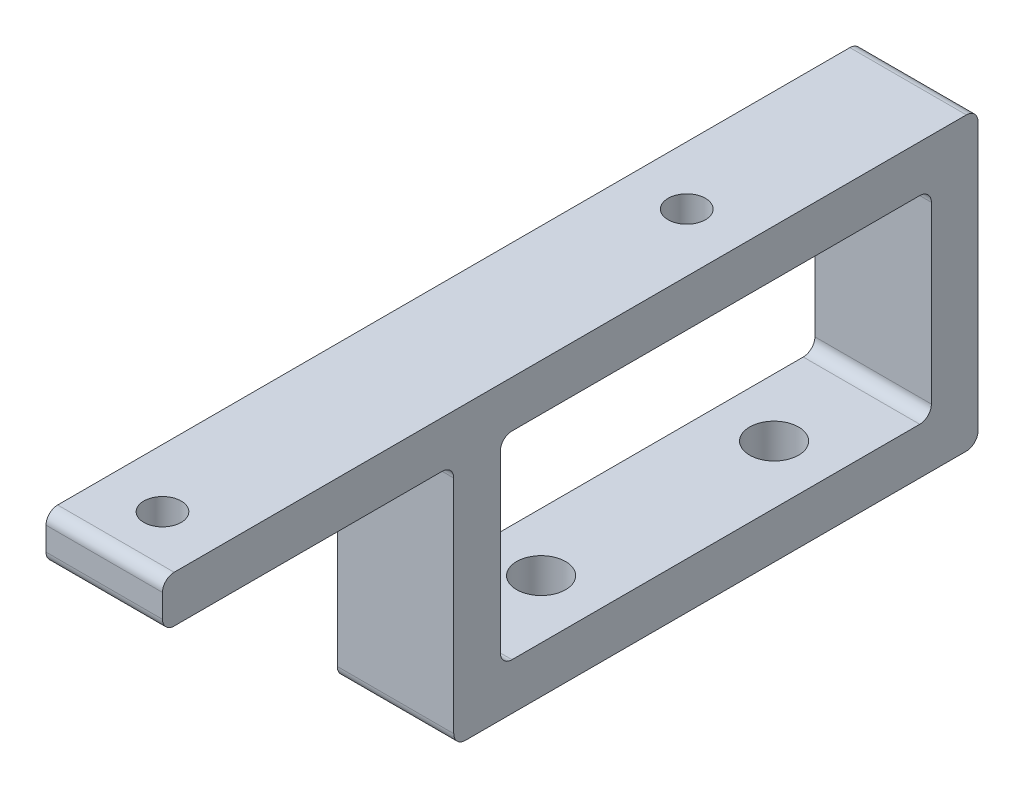
SolidWorks part; units mm, degrees
ref_plane "Front Plane" through (0, 0, 0) normal (0, 0, 1) x (1, 0, 0)
ref_plane "Top Plane" through (0, 0, 0) normal (0, 1, 0) x (1, 0, 0)
ref_plane "Right Plane" through (0, 0, 0) normal (1, 0, 0) x (0, 0, -1)
sketch "Sketch1" plane through (0, 0, 0) normal (1, 0, 0) x (0, 0, -1)
  line L0 (0, 21) -> (0, 0)
  line L1 (0, 25) -> (45, 25)
  line L2 (0, 25) -> (-25, 25)
  line L3 (-25, 25) -> (-25, 21)
  line L4 (45, 0) -> (0, 0)
  line L5 (45, 25) -> (45, 0)
  line L6 (-25, 21) -> (0, 21)
  dimension "D1" = 25
  dimension "D2" = 45
  dimension "D3" = 45
  dimension "D4" = 4
  dimension "D5" = 70
extrude "Boss-Extrude1" add sketch "Sketch1" along normal blind 10
sketch "Sketch3" plane through (0, 0, 0) normal (0, 1, 0) x (1, 0, 0)
  line L0 (0, 22.5) -> (10, 22.5) construction
  line L4 (10, 0) -> (10, 45) construction
  line L8 (5, 12.5) -> (5, 32.5) construction
  line L9 (0, 0) -> (0, 45) construction
  circle A0 centre (5, 32.5) radius 2.1
  circle A1 centre (5, 12.5) radius 2.1
  point P4 (0, 0)
  point P5 (10, 22.5)
  point P6 (0.3278, 22.5)
  point P7 (0, 0)
  point P8 (10, 7.6513)
  point P15 (10, 23.8765)
  point P18 (5, 22.5)
  point P19 (0, 22.5)
  dimension "D1" = 4.2
  dimension "D3" = 20
sketch "Sketch4" plane through (10, 0, 0) normal (1, 0, 0) x (0, 0, -1)
  line L8 (4, 21) -> (41, 21)
  line L12 (4, 4) -> (41, 4)
  line L13 (41, 4) -> (41, 21)
  line L14 (4, 21) -> (4, 4)
  line L15 (41, 21) -> (4, 21)
  line L16 (4, 4) -> (41, 4)
  line L17 (41, 4) -> (41, 21)
  line L18 (4, 21) -> (4, 4)
  dimension "D1" = 4
extrude "Cut-Extrude1" cut sketch "Sketch4" against normal through all
extrude "Cut-Extrude2" cut sketch "Sketch3" along normal up to surface (4 mm away) up to face at (5, 4, -22.5)
sketch "Sketch5" plane through (0, 25, 0) normal (0, 1, 0) x (1, 0, 0)
  line L0 (10, -25) -> (0, -25) construction
  line L3 (5, 25) -> (5, -20) construction
  line L4 (0, 2.5) -> (10, 2.5) construction
  line L5 (0, 45) -> (0, -25) construction
  line L6 (10, 45) -> (10, -25) construction
  circle A0 centre (5, 25) radius 1.6
  circle A1 centre (5, -20) radius 1.6
  point P2 (0, 0)
  point P9 (5, 2.5)
  point P11 (4.2987, 2.5)
  point P15 (5, 2.5)
  dimension "D1" = 3.2
  dimension "D2" = 45
  dimension "D3" = 5
extrude "Cut-Extrude3" cut sketch "Sketch5" against normal up to surface (4 mm away) up to face at (5, 21, -22.5)
fillet "Fillet1" radius 1 10 edges at (5, 21, 0) (5, 21, -41) (5, 4, -41) (5, 25, 25) (5, 21, -4) (5, 4, -4) (5, 25, -45) (5, 0, -45) (5, 0, 0) (5, 21, 25)
